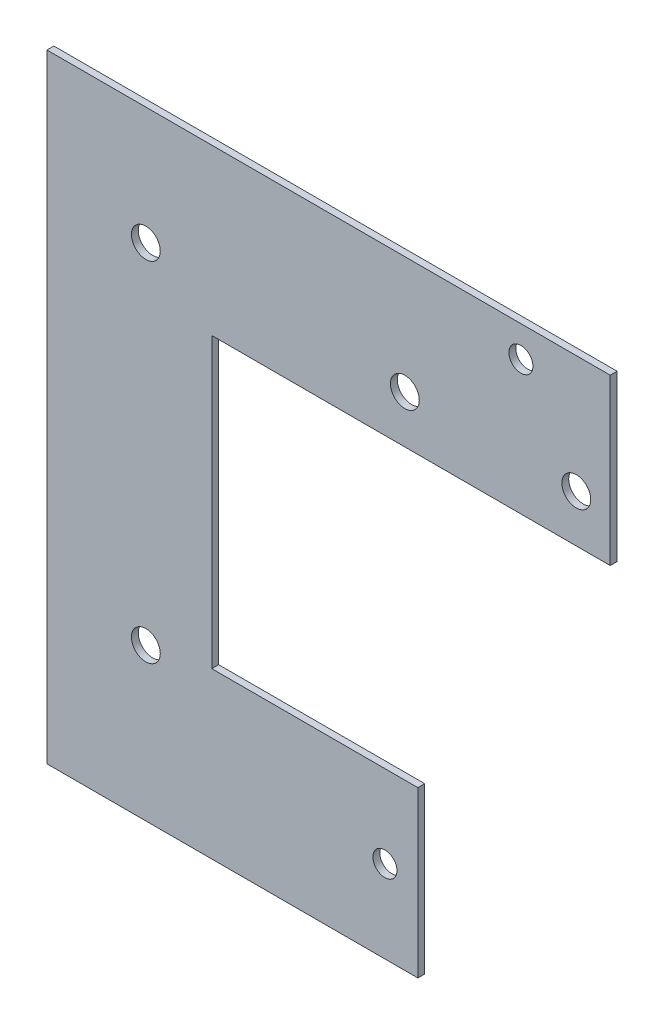
SolidWorks part; units mm, degrees
material "Plain Carbon Steel"
ref_plane "Front Plane" through (0, 0, 0) normal (0, 0, 1) x (1, 0, 0)
ref_plane "Top Plane" through (0, 0, 0) normal (0, 1, 0) x (1, 0, 0)
ref_plane "Right Plane" through (0, 0, 0) normal (1, 0, 0) x (0, 0, -1)
sketch "Sketch1" plane through (0, 0, 0) normal (0, 0, 1) x (1, 0, 0)
  line L1 (0, 24) -> (-59, 24)
  line L2 (-59, 24) -> (-59, -66)
  line L4 (-35, 0) -> (-35, -42)
  line L5 (-35, -66) -> (-59, -66)
  line L6 (-35, 0) -> (23, 0)
  line L7 (23, 0) -> (23, 24)
  line L8 (23, 24) -> (0, 24)
  line L9 (-35, -66) -> (-5, -66)
  line L10 (-5, -66) -> (-5, -42)
  line L11 (-5, -42) -> (-35, -42)
  dimension "D1" = 58
  dimension "D2" = 59
  dimension "D3" = 90
  dimension "D4" = 24
  dimension "D5" = 24
  dimension "D6" = 24
  dimension "D7" = 30
base flange "Base-Flange1" sketch "Sketch1" thickness 1 reverse thickness direction no parameters "D1"=1.6
sketch "Sketch3" plane through (0, 0, 0) normal (0, 0, 1) x (1, 0, 0)
  line L2 (10.0022, 24) -> (10.0022, 19.5)
  line L3 (23, 24) -> (-59, 24) construction
  circle A0 centre (-44.6006, -43.8443) radius 2.1
  circle A1 centre (-44.6006, 6.8926) radius 2.1
  circle A2 centre (-6.8968, 6.9426) radius 2.1
  circle A3 centre (18.0605, 6.8926) radius 2.1
  circle A9 centre (10.0022, 19.5) radius 1.75
  dimension "D1" = 4.2
  dimension "D2" = 4.2
  dimension "D3" = 4.2
  dimension "D4" = 4.2
  dimension "D5" = 3.5
  dimension "D8" = 4.5
extrude "Cut-Extrude1" cut sketch "Sketch3" against normal blind 40
sketch "Sketch4" plane through (0, 0, 0) normal (0, 0, 1) x (1, 0, 0)
  circle A0 centre (-9.7917, -54) radius 1.75
extrude "Cut-Extrude2" cut sketch "Sketch4" against normal blind 10 normal cut yes
sketch "Bend-Lines1" [suppressed] plane through (0, 0, 0) normal (0, 1, 0) x (1, 0, 0)
sketch "Bounding-Box1" [suppressed] plane through (0, 0, 0) normal (0, 1, 0) x (1, 0, 0)
sheet metal parameters "Sheet-Metal8" thickness 1 parameters "D1"=1.6
flat pattern "Flat-Pattern8" [suppressed]
sketch "Bend-Lines2" plane through (0, 0, 0) normal (0, 1, 0) x (1, 0, 0)
sketch3d "Bounding-Box2" [suppressed]
  line L0 (-59, -56, 0) -> (23, -56, 0) construction
  line L1 (-59, 24, 0) -> (23, 24, 0) construction
  line L2 (-59, -56, 0) -> (-59, 24, 0) construction
  line L3 (23, -56, 0) -> (23, 24, 0) construction
sheet metal parameters "Sheet-Metal16" thickness 1 parameters "D1"=1.6
flat pattern "Flat-Pattern8"
sketch "Bend-Lines2" plane through (0, 0, 0) normal (0, 1, 0) x (1, 0, 0)
sketch3d "Bounding-Box2" [suppressed]
  line L0 (23, 24, 0) -> (23, -66, 0) construction
  line L1 (-59, 24, 0) -> (-59, -66, 0) construction
  line L2 (23, 24, 0) -> (-59, 24, 0) construction
  line L3 (23, -66, 0) -> (-59, -66, 0) construction
sheet metal parameters "Sheet-Metal17" thickness 1 parameters "D1"=1.6
flat pattern "Flat-Pattern8"
sketch "Bend-Lines2" plane through (0, 0, 0) normal (0, 1, 0) x (1, 0, 0)
sketch3d "Bounding-Box2" [suppressed]
  line L0 (23, 24, 0) -> (23, -66, 0) construction
  line L1 (-59, 24, 0) -> (-59, -66, 0) construction
  line L2 (23, 24, 0) -> (-59, 24, 0) construction
  line L3 (23, -66, 0) -> (-59, -66, 0) construction
